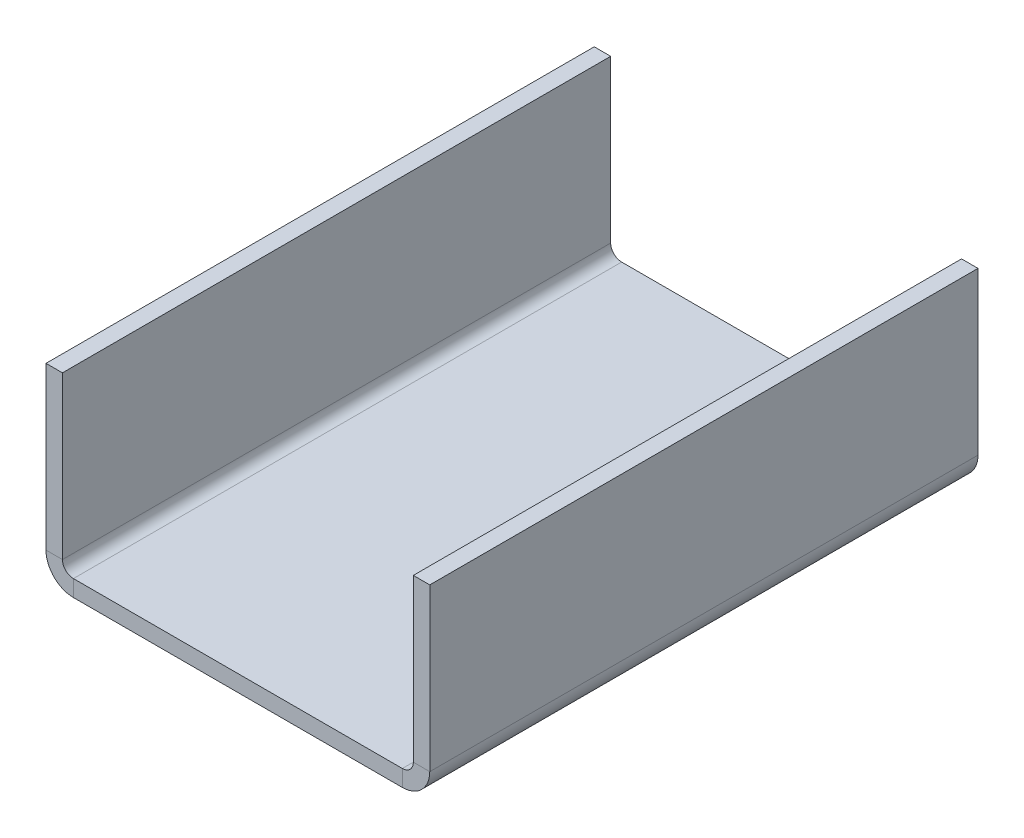
SolidWorks part; units mm, degrees
ref_plane "Front Plane" through (0, 0, 0) normal (0, 0, 1) x (1, 0, 0)
ref_plane "Top Plane" through (0, 0, 0) normal (0, 1, 0) x (1, 0, 0)
ref_plane "Right Plane" through (0, 0, 0) normal (1, 0, 0) x (0, 0, -1)
sketch "Sketch1" plane through (0, 0, 0) normal (0, 1, 0) x (1, 0, 0)
  line L1 (-65, 50) -> (65, 50)
  line L2 (-65, 50) -> (-65, -50)
  line L3 (-65, -50) -> (65, -50)
  line L4 (65, 50) -> (65, -50)
  point P0 (0, 0)
  dimension "D1" = 100
  dimension "D2" = 130
base flange "Base-Flange1" sketch "Sketch1" thickness 3 reverse thickness direction no parameters "D1"=2
sketch "Sketch9" plane through (0, 0, 0) normal (0, 1, 0) x (1, 0, 0)
  line L0 (-30, 50) -> (-30, -50)
  line L1 (65, 50) -> (-65, 50) construction
  line L2 (-65, -50) -> (65, -50) construction
  line L3 (30, 50) -> (30, -50)
  line L4 (0, 50) -> (0, -50) construction
  dimension "D1" = 60
sketched bend "Sketched Bend1" thickness 3 bend on line 2 starts at 0 ends at 5.4978 away from the fixed side along (1, 0, 0) bending towards (0, 1, 0) bend on line 1 starts at 0 ends at 5.4978 away from the fixed side along (-1, 0, 0) bending towards (0, 1, 0) parameters "D1"=0
bend "SketchBend1" bend radius 2 bend angle 90 parameters "D5"=1
bend "SketchBend2" bend radius 0 bend angle 90 parameters "D5"=2
